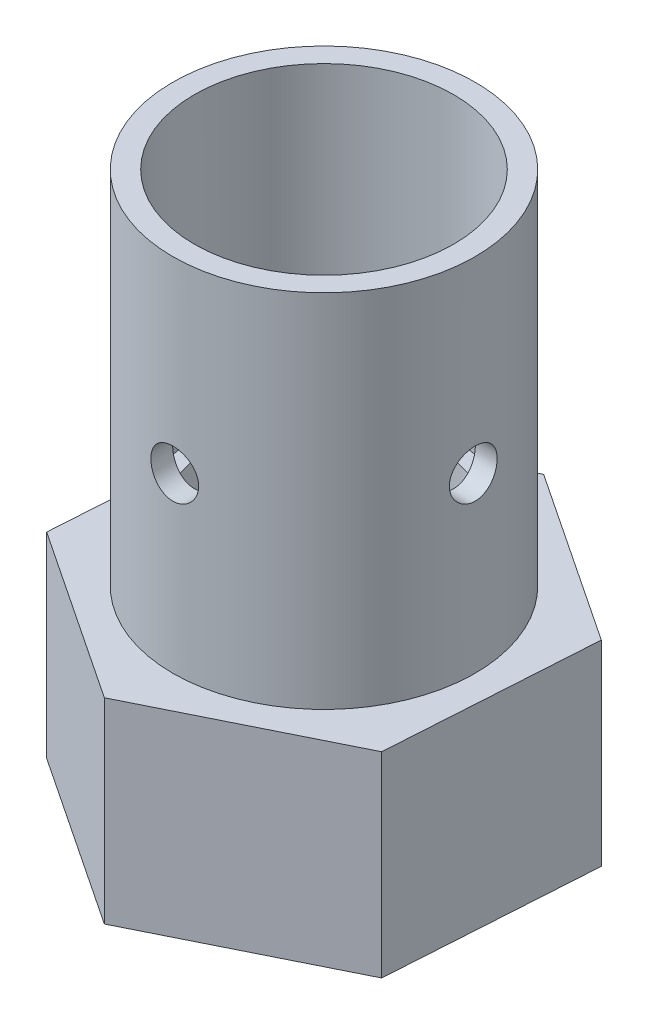
SolidWorks part; units mm, degrees
ref_plane "Front Plane" through (0, 0, 0) normal (0, 0, 1) x (1, 0, 0)
ref_plane "Top Plane" through (0, 0, 0) normal (0, 1, 0) x (1, 0, 0)
ref_plane "Right Plane" through (0, 0, 0) normal (1, 0, 0) x (0, 0, -1)
sketch "Sketch1" plane through (0, 0, 0) normal (0, 1, 0) x (1, 0, 0)
  line L1 (14.4207, -9.5939) -> (15.5189, 7.6917)
  line L2 (15.5189, 7.6917) -> (1.0982, 17.2857)
  line L3 (1.0982, 17.2857) -> (-14.4207, 9.5939)
  line L4 (-14.4207, 9.5939) -> (-15.5189, -7.6917)
  line L5 (-15.5189, -7.6917) -> (-1.0982, -17.2857)
  line L6 (-1.0982, -17.2857) -> (14.4207, -9.5939)
  circle A1 centre (0, 0) radius 10.85
  circle A2 centre (0, 0) radius 12.65
  circle A3 centre (0, 0) radius 15 construction
  circle A4 centre (0, 0) radius 9.5
  dimension "D1" = 21.7
  dimension "D2" = 25.3
  dimension "D4" = 19
  dimension "D3" = 30
extrude "Boss-Extrude1" add sketch "Sketch1" along normal blind 30.2 contours A2 A1 region at (-12.2922, 0, 0)
extrude "Boss-Extrude2" add sketch "Sketch1<3>" against normal blind 16.4 separate body contours L5 L6 L1 L2 L3 L4 A2 region at (6.4549, 0, 13.0235)
sketch "Sketch1<3>" plane through (0, 0, 0) normal (0, 1, 0) x (1, 0, 0) same geometry as "Sketch1"
extrude "Boss-Extrude3" add sketch "Sketch1<4>" against normal blind 16.4 contours A1 A4 | A2 A1 region at (-10.5431, 0, 0) region at (-12.2922, 0, 0)
sketch "Sketch1<4>" plane through (0, 0, 0) normal (0, 1, 0) x (1, 0, 0) same geometry as "Sketch1"
extrude "Boss-Extrude4" add sketch "Sketch1<5>" along normal blind 5.2 contours A1 A4 region at (-10.5431, 0, 0)
sketch "Sketch1<5>" plane through (0, 0, 0) normal (0, 1, 0) x (1, 0, 0) same geometry as "Sketch1"
thread "Thread1" pitch 1.25 method extrude profile "Thread Profile1" start angle 0, offset 0, length 16.4, pitch 1.25, diameter 19
ref_plane "Plane1" through (9.5, -16.4, 0) normal (0, 0, 1) x (1, 0, 0)
sketch "Thread Profile1" plane through (9.5, -16.4, 0) normal (0, 0, 1) x (1, 0, 0)
  line L0 (0, 0) -> (0, 1.25) construction
  line L11 (0, 0) -> (0, 1.0937)
  line L12 (0, 1.0937) -> (-0.6766, 0.7031)
  line L13 (-0.6766, 0.7031) -> (-0.6766, 0.3906)
  line L15 (-0.6766, 0.3906) -> (0, 0)
  line L17 (-0.6766, 0.5469) -> (0, 0.5469) construction
  point P2 (0, 0)
  dimension "Pitch" = 1.25
  dimension "Profile_Angle" = 60
  dimension "Profile_Land" = 0.3125
  dimension "Profile_Height" = 0.6766
sketch "Sketch2" plane through (0, 0, 0) normal (0, 0, 1) x (1, 0, 0)
  line L0 (-1.0982, 0) -> (14.4207, 0) construction
  circle A0 centre (0, 14.48) radius 2
  dimension "D1" = 14.48
extrude "Cut-Extrude1" cut sketch "Sketch2" along normal through all
sketch "Sketch3" plane through (0, 0, 0) normal (1, 0, 0) x (0, 0, -1)
  line L0 (-9.5939, 0) -> (7.6917, 0) construction
  circle A0 centre (0, 14.48) radius 2
  dimension "D1" = 14.48
extrude "Cut-Extrude2" cut sketch "Sketch3" against normal through all and the other way through all
